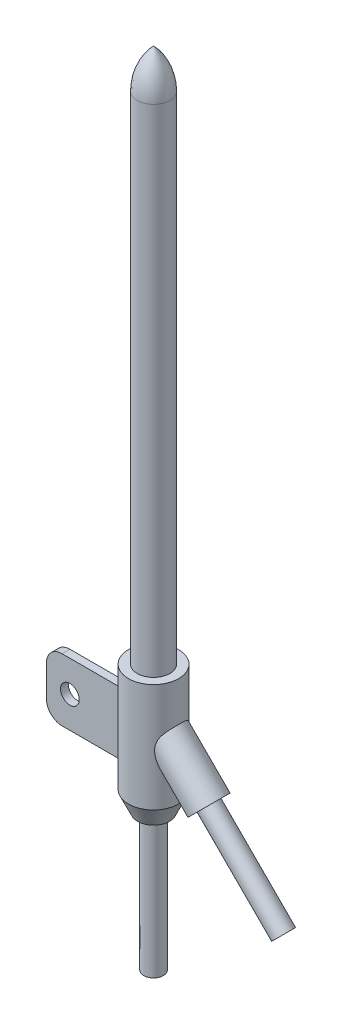
SolidWorks part; units mm, degrees
ref_plane "Front Plane" through (0, 0, 0) normal (0, 0, 1) x (1, 0, 0)
ref_plane "Top Plane" through (0, 0, 0) normal (0, 1, 0) x (1, 0, 0)
ref_plane "Right Plane" through (0, 0, 0) normal (1, 0, 0) x (0, 0, -1)
sketch "Sketch2" plane through (0, 0, 0) normal (0, 1, 0) x (1, 0, 0)
  circle A0 centre (0, 0) radius 2.085
  dimension "D1" = 4.17
extrude "Boss-Extrude1" add sketch "Sketch2" along normal blind 63.5
sketch "Sketch3" plane through (0, 0, 0) normal (0, 0, 1) x (1, 0, 0)
  line L0 (2.085, 63.5) -> (2.085, 60.967) construction
  line L1 (2.085, 0) -> (2.085, 63.5) construction
  line L2 (0, 63.5) -> (0, 68.5)
  line L3 (2.085, 63.5) -> (-2.085, 63.5) construction
  line L4 (2.085, 63.5) -> (0, 63.5)
  arc A0 (2.085, 63.5) -> (0, 68.5) centre (-4.9527, 63.5) ccw
  dimension "D1" = 5
revolve "Revolve2" add sketch "Sketch3" angle 360 about L2
sketch "Sketch4" plane through (0, 0, 0) normal (0, 0, 1) x (1, 0, 0)
  line L0 (0, 0) -> (0, -16.4)
  line L1 (0, -16.4) -> (2.05, -16.4)
  line L2 (2.05, -16.4) -> (3.21, -13.9)
  line L3 (3.21, -13.9) -> (3.21, 0)
  line L4 (3.21, 0) -> (0, 0)
  line L5 (0, 0) -> (0, -13.3708) construction
  point P7 (2.05, -7.8844)
  dimension "D1" = 6.42
  dimension "D2" = 4.1
  dimension "D3" = 2.5
  dimension "D4" = 16.4
revolve "Revolve3" add sketch "Sketch4" angle 360 about L5
sketch "Sketch5" plane through (0, 0, 0) normal (0, 0, 1) x (1, 0, 0)
  line L0 (0, 0) -> (0, -16.4) construction
  line L1 (-2.05, -16.4) -> (2.05, -16.4) construction
  line L2 (0, -8.2) -> (3.21, -8.2) construction
  line L3 (3.21, -13.9) -> (3.21, 0) construction
  line L4 (0, -8.2) -> (-3.21, -8.2) construction
  line L5 (-3.21, 0) -> (-3.21, -13.9) construction
  point P13 (-3.21, -8.2)
  point P14 (3.21, -8.2)
ref_plane "Plane2" through (0, -8.2, 0) normal (0, 1, 0) x (1, 0, 0)
sketch "Sketch6" plane through (0, -8.2, 0) normal (0, 1, 0) x (1, 0, 0)
  line L0 (3.21, -6.2703) -> (3.21, 6.2703) construction
  point P2 (3.21, 0)
ref_plane "Plane3" through (5.705, -5.705, 0) normal (-0.7071, 0.7071, 0) x (0, 0, -1)
sketch "Sketch7" plane through (5.705, -5.705, 0) normal (-0.7071, 0.7071, 0) x (0, 0, -1)
  circle A0 centre (0, 3.5285) radius 2.2
  dimension "D1" = 4.4
extrude "Boss-Extrude2" add sketch "Sketch7" against normal blind 5.5 and the other way up to next
sketch "Sketch8" plane through (9.5941, -9.5941, 0) normal (0.7071, -0.7071, 0) x (0, 0, -1)
  circle A0 centre (0, -3.5285) radius 1.25
  circle A1 centre (0, -3.5285) radius 2.2 construction
  dimension "D1" = 2.5
extrude "Boss-Extrude3" add sketch "Sketch8" along normal blind 13.5
sketch "Sketch9" plane through (0, -16.4, 0) normal (0, -1, 0) x (1, 0, 0)
  circle A0 centre (0, 0) radius 1.25
  circle A1 centre (0, 0) radius 2.05 construction
  dimension "D1" = 2.5
extrude "Boss-Extrude4" add sketch "Sketch9" along normal blind 17.5
ref_plane "Plane4" through (-3.21, 0, 0) normal (1, 0, 0) x (0, 0, -1)
sketch "Sketch10" plane through (-3.21, 0, 0) normal (1, 0, 0) x (0, 0, -1)
  line L1 (0.5, -12.2) -> (-0.5, -12.2)
  line L2 (0.5, -12.2) -> (0.5, -4.2)
  line L3 (0.5, -4.2) -> (-0.5, -4.2)
  line L4 (-0.5, -12.2) -> (-0.5, -4.2)
  line L5 (0.5, -12.2) -> (-0.5, -4.2) construction
  line L6 (0.5, -4.2) -> (-0.5, -12.2) construction
  point P0 (0, -8.2)
  dimension "D1" = 8
  dimension "D2" = 1
extrude "Boss-Extrude5" add sketch "Sketch10" against normal blind 10 and the other way up to surface other way up to face at (0, 0, 3.21)
hole_wizard "M2 Clearance Hole1" positions "Sketch11" profile "Sketch12" hole size "M2" standard "ANSI Metric" end condition through all
sketch "Sketch11" plane through (0, 0, 0.5) normal (0, 0, 1) x (1, 0, 0)
  line L0 (-13.21, -8.2) -> (-10.21, -8.2) construction
  line L1 (-13.21, -4.2) -> (-13.21, -12.2) construction
  point P2 (-10.21, -8.2)
  dimension "D1" = 3
sketch "Sketch12" plane through (-10.21, -8.2, 0.5) normal (1, 0, 0) x (0, -1, 0)
  line L0 (0, 0) -> (0, 3.71)
  line L1 (0, 3.71) -> (1.2, 3.71)
  line L2 (1.2, 3.71) -> (1.2, 0)
  line L5 (1.2, 0) -> (0, 0)
  line L11 (0, -6.35) -> (0, 107.95) construction
  dimension "Thru Hole Dia." = 2.4
  dimension "Thru Hole Depth" = 3.71
fillet "Fillet1" radius 2 2 edges at (-13.21, -12.2, 0) (-13.21, -4.2, 0)
